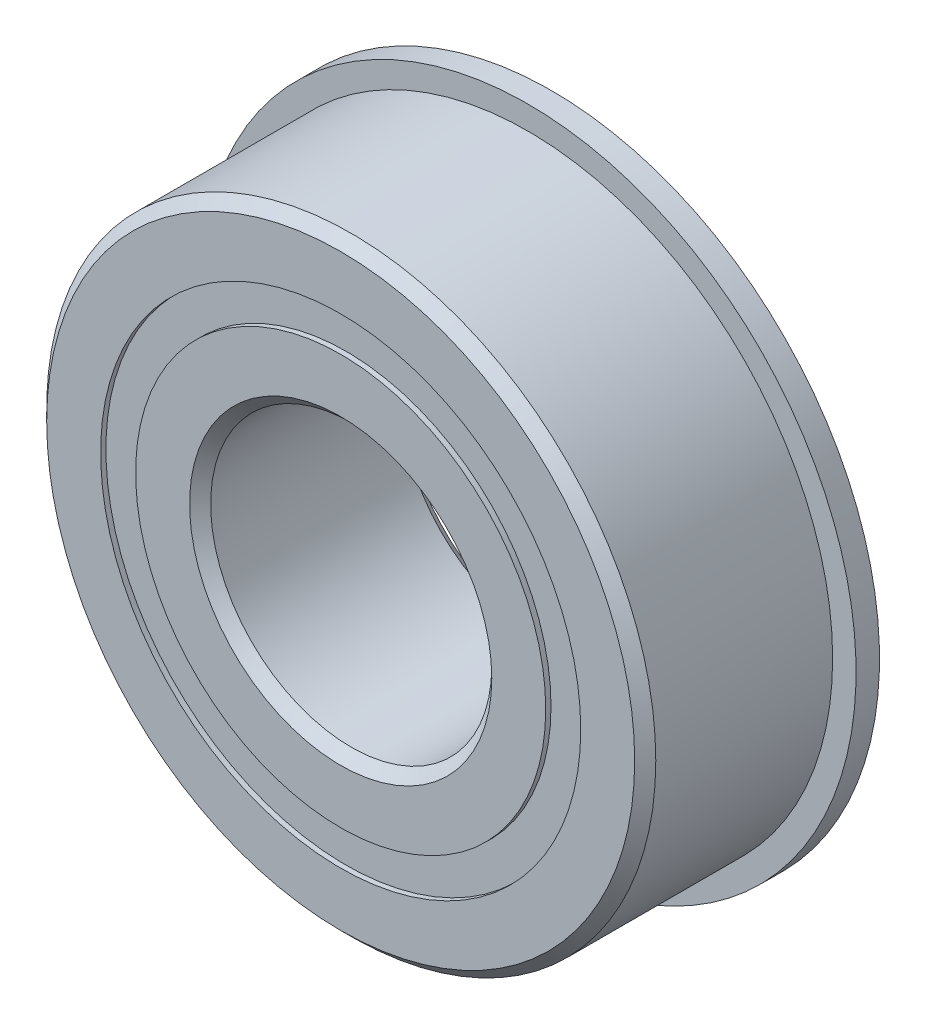
SolidWorks part; units mm, degrees
ref_plane "Front Plane" through (0, 0, 0) normal (0, 0, 1) x (1, 0, 0)
ref_plane "Top Plane" through (0, 0, 0) normal (0, 1, 0) x (1, 0, 0)
ref_plane "Right Plane" through (0, 0, 0) normal (1, 0, 0) x (0, 0, -1)
sketch "Sketch1" plane through (0, 0, 0) normal (1, 0, 0) x (0, 0, -1)
  line L0 (-7.1437, 0) -> (7.1437, 0) construction
  line L1 (0, 20.6375) -> (0, -20.6375) construction
  line L2 (6.4294, 20.6375) -> (-6.4294, 20.6375)
  line L3 (-6.4294, 20.6375) -> (-7.1438, 19.9231)
  line L4 (-7.1438, 19.9231) -> (-7.1438, 16.2675)
  line L5 (-7.1438, 16.2675) -> (-3.175, 16.2675)
  line L6 (7.1437, 16.2675) -> (3.175, 16.2675)
  line L7 (7.1437, 19.9231) -> (7.1437, 16.2675)
  line L8 (6.4294, 20.6375) -> (7.1437, 19.9231)
  line L9 (0, 20.6375) -> (0, 15.0813) construction
  line L10 (0, 15.0813) -> (0, 9.525) construction
  arc A0 (-3.175, 16.2675) -> (3.175, 16.2675) centre (0, 15.0813) cw
  point P14 (0, 9.525)
  dimension "Width" = 14.2875
  dimension "OD" = 41.275
  dimension "D1" = 45
  dimension "D2" = 0.7144
  dimension "Shaft Dia" = 19.05
  dimension "D3" = 6.35
  dimension "D4" = 1.1863
revolve "Revolve1" add sketch "Sketch1" angle 360 about L0
sketch "Sketch3" plane through (0, 0, 0) normal (1, 0, 0) x (0, 0, -1)
  line L0 (-7.1437, 13.895) -> (-3.175, 13.895)
  line L1 (0, 20.6375) -> (0, -20.6375) construction
  line L2 (-7.1438, 19.9231) -> (-7.1438, 16.2675) construction
  line L3 (-7.1437, 13.895) -> (-7.1437, 10.2394)
  line L4 (-6.4294, 20.6375) -> (-7.1438, 19.9231) construction
  line L5 (-7.1437, 10.2394) -> (-6.4294, 9.525)
  line L6 (-6.4294, 9.525) -> (6.4294, 9.525)
  line L7 (6.4294, 20.6375) -> (6.4294, -20.6375) construction
  line L8 (6.4294, 9.525) -> (7.1437, 10.2394)
  line L9 (7.1437, -19.9231) -> (7.1437, 19.9231) construction
  line L10 (7.1437, 10.2394) -> (7.1437, 13.895)
  line L11 (7.1437, 13.895) -> (3.175, 13.895)
  line L13 (6.4294, 20.6375) -> (7.1437, 19.9231) construction
  arc A0 (3.175, 16.2675) -> (-3.175, 16.2675) centre (0, 15.0813) ccw construction
  arc A1 (3.175, 13.895) -> (-3.175, 13.895) centre (0, 15.0812) cw
revolve "Revolve3" add sketch "Sketch3" angle 360 about L0
sketch "Sketch4" plane through (0, 0, 0) normal (1, 0, 0) x (0, 0, -1)
  line L0 (-3.3894, 15.0813) -> (3.3894, 15.0813)
  arc A2 (-3.3894, 15.0813) -> (3.3894, 15.0813) centre (0, 15.0813) cw
  arc A3 (3.175, 16.2675) -> (-3.175, 16.2675) centre (0, 15.0813) ccw construction
revolve "Revolve4" add sketch "Sketch4" angle 360 about L0
ref_axis "Axis1" through (0, 0, -7.1437) along (0, 0, 1)
pattern_circular "CirPattern1" count 14 every 25.714 about axis through (0, 0, -7.1437) along (0, 0, 1) of bodies 104
sketch "Sketch5" plane through (0, 0, 0) normal (1, 0, 0) x (0, 0, -1)
  line L0 (-7.1438, 16.2675) -> (-3.175, 16.2675) construction
  line L1 (-6.7866, 16.2675) -> (-3.3894, 16.2675)
  line L2 (-6.7866, 16.2675) -> (-6.7866, 13.895)
  line L3 (-6.7866, 13.895) -> (-3.3894, 13.895)
  line L4 (-3.3894, 16.2675) -> (-3.3894, 13.895)
  line L5 (-7.1437, 13.895) -> (-3.175, 13.895) construction
  line L6 (7.1437, 16.2675) -> (3.175, 16.2675) construction
  line L7 (6.7866, 16.2675) -> (3.3894, 16.2675)
  line L8 (6.7866, 16.2675) -> (6.7866, 13.895)
  line L9 (6.7866, 13.895) -> (3.3894, 13.895)
  line L10 (3.3894, 16.2675) -> (3.3894, 13.895)
  line L11 (7.1437, 13.895) -> (3.175, 13.895) construction
  line L12 (-6.4294, 20.6375) -> (-7.1438, 19.9231) construction
  point P18 (-6.7866, 20.2803)
revolve "Revolve5" add sketch "Sketch5" angle 360 about L0
sketch "Sketch6" plane through (0, 0, 0) normal (1, 0, 0) x (0, 0, -1)
  line L0 (7.1437, 0) -> (-7.1437, 0) construction
  line L1 (7.1437, 16.2675) -> (5.5563, 16.2675)
  line L2 (7.1437, 16.2675) -> (7.1437, 22.225)
  line L3 (7.1437, 22.225) -> (5.5563, 22.225)
  line L4 (5.5563, 16.2675) -> (5.5563, 22.225)
  dimension "Th" = 1.5875
  dimension "Flange OD" = 44.45
revolve "Revolve6" add sketch "Sketch6" angle 360 about L0
equation "\"D2@Sketch1\" = \"Width@Sketch1\"*.05"
equation "\"D3@Sketch1\" = \"Width@Sketch1\"/2.25"
equation "\"D4@Sketch1\" = (((\"OD@Sketch1\"-\"Width@Sketch1\")/2)/3.25)/3.5"
equation "\"D2@CirPattern1\" = 360/\"Balls@CirPattern1\""
